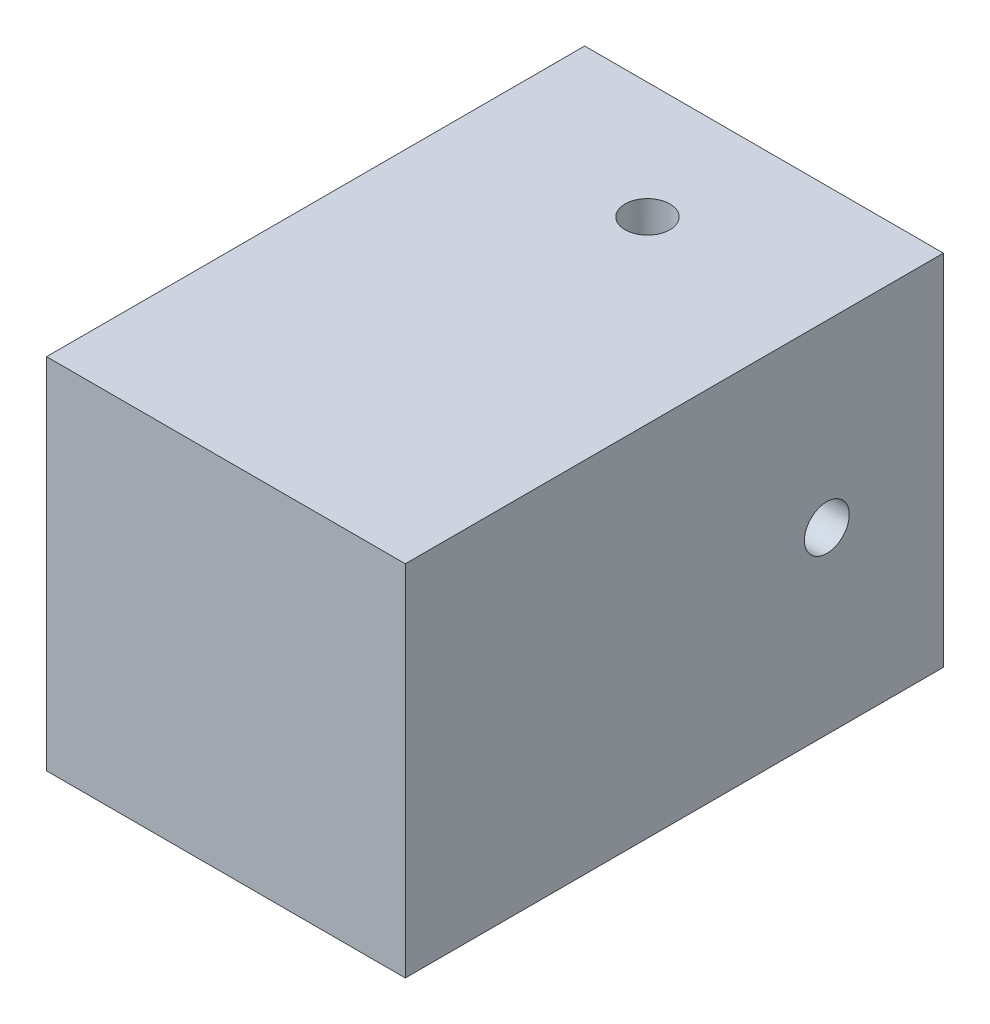
SolidWorks part; units mm, degrees
material "PETG-FDM"
ref_plane "前视基准面" through (0, 0, 0) normal (0, 0, 1) x (1, 0, 0)
ref_plane "上视基准面" through (0, 0, 0) normal (0, 1, 0) x (1, 0, 0)
ref_plane "右视基准面" through (0, 0, 0) normal (1, 0, 0) x (0, 0, -1)
other "Configuration Table"
sketch "草图1" plane through (0, 0, 0) normal (0, 0, 1) x (1, 0, 0)
  line L7 (-20, -20) -> (20, -20)
  line L8 (-20, -20) -> (-20, 20)
  line L9 (-20, 20) -> (20, 20)
  line L10 (20, -20) -> (20, 20)
  line L11 (-20, -20) -> (20, 20) construction
  line L12 (-20, 20) -> (20, -20) construction
  point P0 (0, 0)
  dimension "D1" = 40
  dimension "D2" = 40
extrude "凸台-拉伸1" add sketch "草图1" along normal blind 60
sketch "草图7" plane through (0, -20, 0) normal (0, -1, 0) x (1, 0, 0)
  line L0 (-20, 20) -> (20, 20) construction
  line L1 (-20, 60) -> (-20, 0) construction
  line L2 (20, 60) -> (20, 0) construction
  line L3 (-20, 0) -> (20, 0) construction
  line L4 (0, 0) -> (0, 20) construction
  circle A0 centre (0, 13) radius 2.5
  dimension "D2" = 5
  dimension "D1" = 20
  dimension "D3" = 7
extrude "切除-拉伸1" cut sketch "草图7" against normal blind 10
sketch "草图8" plane through (20, 0, 0) normal (1, 0, 0) x (0, 0, -1)
  line L0 (-20, 20) -> (-20, -20) construction
  line L1 (-60, 20) -> (0, 20) construction
  line L2 (-60, -20) -> (0, -20) construction
  line L3 (0, 0) -> (-20, 0) construction
  line L4 (0, -20) -> (0, 20) construction
  circle A0 centre (-13, 0) radius 2.5
  dimension "D2" = 5
  dimension "D1" = 20
  dimension "D3" = 7
extrude "切除-拉伸2" cut sketch "草图8" against normal blind 10
mirror "镜向1" about plane through (0, 0, 0) normal (0, 1, 0) of "切除-拉伸1"
mirror "镜向2" about plane through (0, 0, 0) normal (1, 0, 0) of "切除-拉伸2"
sketch "草图9" plane through (0, 0, 60) normal (0, 0, 1) x (1, 0, 0)
  circle A0 centre (0, 0) radius 28.2843
sketch "草图10" plane through (0, 0, 0) normal (0, 0, -1) x (-1, 0, 0)
  line L1 (-15, 15) -> (15, 15)
  line L2 (-15, 15) -> (-15, -15)
  line L3 (-15, -15) -> (15, -15)
  line L4 (15, 15) -> (15, -15)
  line L5 (-15, 15) -> (15, -15) construction
  line L6 (-15, -15) -> (15, 15) construction
  point P0 (0, 0)
  dimension "D1" = 30
  dimension "D2" = 30
extrude "切除-拉伸3" cut sketch "草图10" against normal blind 50
